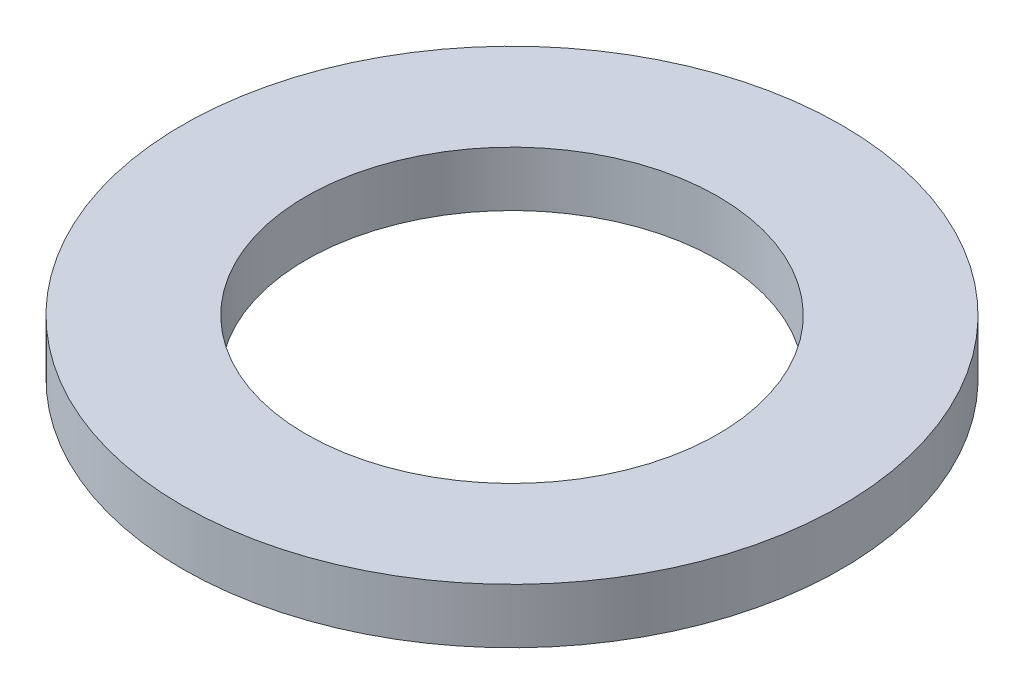
SolidWorks part; units mm, degrees
ref_plane "Front Plane" through (0, 0, 0) normal (0, 0, 1) x (1, 0, 0)
ref_plane "Top Plane" through (0, 0, 0) normal (0, 1, 0) x (1, 0, 0)
ref_plane "Right Plane" through (0, 0, 0) normal (1, 0, 0) x (0, 0, -1)
sketch "Sketch1" plane through (0, 0, 0) normal (0, 1, 0) x (1, 0, 0)
  circle A0 centre (0, 0) radius 60
  dimension "FLANGE_OD" = 120
extrude "Boss-Extrude1" add sketch "Sketch1" along normal blind 10
sketch "Sketch2" plane through (0, 0, 0) normal (0, 1, 0) x (1, 0, 0)
  circle A0 centre (0, 0) radius 37.5
  dimension "BORE_D" = 75
extrude "Cut-Extrude1" cut sketch "Sketch2" along normal through all
sketch "Sketch3" plane through (0, 10, 0) normal (0, 1, 0) x (1, 0, 0)
  circle A0 centre (0, 0) radius 24.049 construction
  circle A1 centre (-24.049, 0) radius 3.8575
  dimension "BOLT_D" = 7.7151
  dimension "BOLT_PCD" = 48.098
extrude "Cut-Extrude2" cut sketch "Sketch3" against normal blind 8.5909 rebuild error yes
pattern_circular "CirPattern1" count 5 over 360 rebuild error yes
